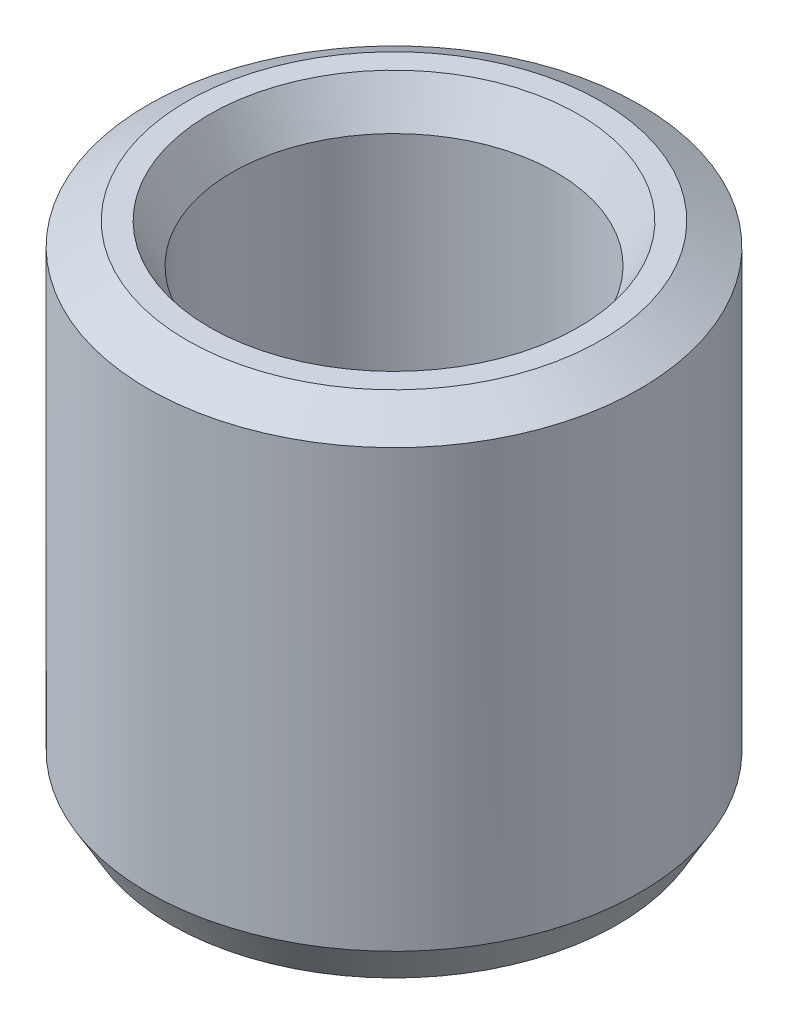
SolidWorks part; units mm, degrees
ref_plane "Front Plane" through (0, 0, 0) normal (0, 0, 1) x (1, 0, 0)
ref_plane "Top Plane" through (0, 0, 0) normal (0, 1, 0) x (1, 0, 0)
ref_plane "Right Plane" through (0, 0, 0) normal (1, 0, 0) x (0, 0, -1)
sketch "Sketch1" plane through (0, 0, 0) normal (0, 1, 0) x (1, 0, 0)
  circle A0 centre (0, 0) radius 10
  dimension "SLEEVE_OD" = 20
extrude "Boss-Extrude1" add sketch "Sketch1" along normal blind 20.2315
sketch "Sketch2" plane through (0, 0, 0) normal (0, 1, 0) x (1, 0, 0)
  circle A0 centre (0, 0) radius 6.5841
  dimension "BORE_D" = 13.1682
extrude "Cut-Extrude1" cut sketch "Sketch2" along normal through all
chamfer "Chamfer1" distance 0.9151 angle 60 4 edges at (0, 20.2315, 6.5841) (0, 0, 6.5841) (0, 0, 10) (0, 20.2315, 10) first distance on face at (0, 20.2315, 6.5841) first distance on face at (0, 0, 6.5841) first distance on face at (0, 20.2315, 10)
